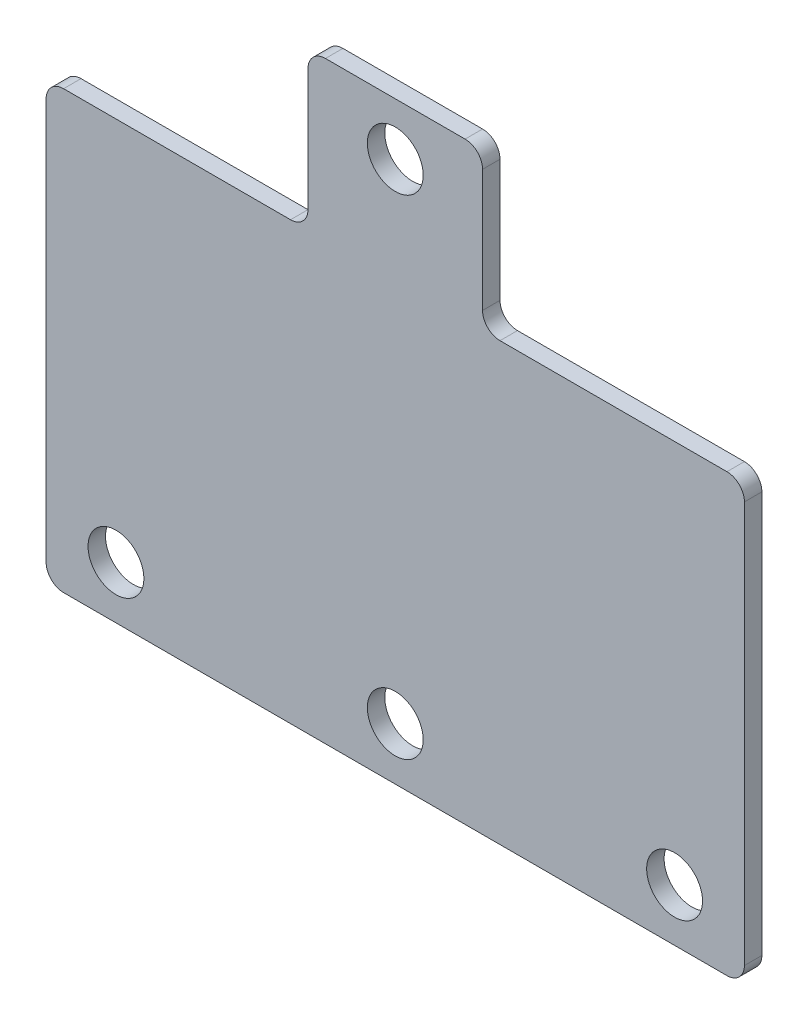
SolidWorks part; units mm, degrees
material "Thornel Mat VMA"
ref_plane "前视基准面" through (0, 0, 0) normal (0, 0, 1) x (1, 0, 0)
ref_plane "上视基准面" through (0, 0, 0) normal (0, 1, 0) x (1, 0, 0)
ref_plane "右视基准面" through (0, 0, 0) normal (1, 0, 0) x (0, 0, -1)
sketch "Sketch1" plane through (0, 0, 0) normal (0, 0, 1) x (1, 0, 0)
  line L1 (-20, 12.5) -> (20, 12.5)
  line L2 (-20, 12.5) -> (-20, -12.5)
  line L3 (-20, -12.5) -> (20, -12.5)
  line L4 (20, 12.5) -> (20, -12.5)
  line L5 (-20, 12.5) -> (20, -12.5) construction
  line L6 (-20, -12.5) -> (20, 12.5) construction
  circle A0 centre (0, -9.5) radius 1.6
  circle A1 centre (16, -9.5) radius 1.6
  circle A2 centre (-16, -9.5) radius 1.6
  point P0 (0, 0)
  dimension "D3" = 3.2
  dimension "D4" = 3
  dimension "D5" = 3.2
  dimension "D6" = 3
  dimension "D7" = 4
  dimension "D8" = 3.2
  dimension "D9" = 4
  dimension "D1" = 40
  dimension "D2" = 25
  dimension "D10" = 3
extrude "Boss-Extrude1" add sketch "Sketch1" along normal blind 1
sketch "Sketch2" plane through (0, 0, 1) normal (0, 0, 1) x (1, 0, 0)
  line L0 (20, 12.5) -> (-20, 12.5) construction
  line L1 (-5, 21.5) -> (5, 21.5)
  line L2 (-5, 21.5) -> (-5, 3.5)
  line L3 (-5, 3.5) -> (5, 3.5)
  line L4 (5, 21.5) -> (5, 3.5)
  line L5 (-5, 21.5) -> (5, 3.5) construction
  line L6 (-5, 3.5) -> (5, 21.5) construction
  circle A1 centre (0, 18.5) radius 1.6
  point P0 (0, 12.5)
  dimension "D3" = 3
  dimension "D2" = 3.2
  dimension "D1" = 18
extrude "Boss-Extrude2" add sketch "Sketch2" against normal up to surface (1 mm away) up to face at (0, 0, 0)
fillet "Fillet1" radius 1 8 edges at (20, -12.5, 0.5) (20, 12.5, 0.5) (5, 12.5, 0.5) (5, 21.5, 0.5) (-20, -12.5, 0.5) (-20, 12.5, 0.5) (-5, 21.5, 0.5) (-5, 12.5, 0.5)
